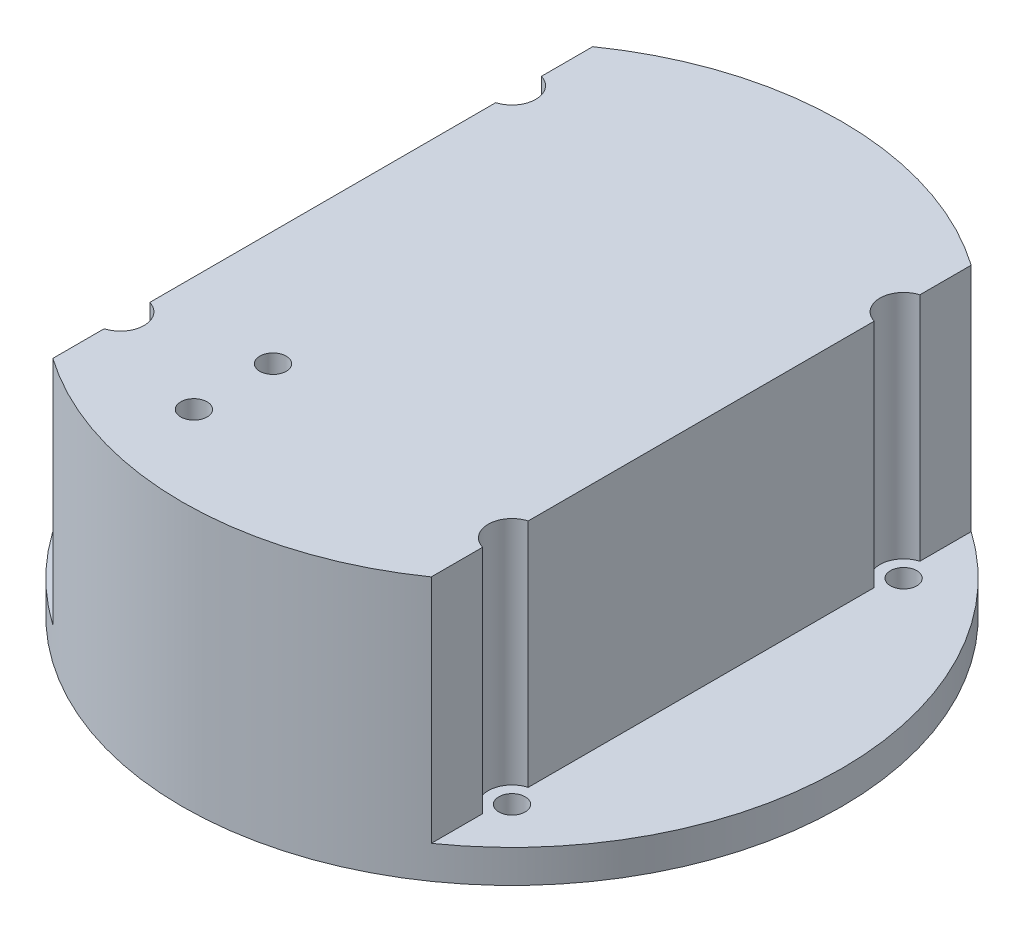
SolidWorks part; units mm, degrees
ref_plane "Ön Düzlem" through (0, 0, 0) normal (0, 0, 1) x (1, 0, 0)
ref_plane "Üst Düzlem" through (0, 0, 0) normal (0, 1, 0) x (1, 0, 0)
ref_plane "Sağ Düzlem" through (0, 0, 0) normal (1, 0, 0) x (0, 0, -1)
sketch "ara düzlem" plane through (0, 0, 0) normal (0, 1, 0) x (1, 0, 0)
  line L0 (-28.7, 40.9428) -> (-28.7, -40.9428)
  line L1 (0, 0) -> (0, 50) construction
  line L2 (28.7, 40.9428) -> (28.7, -40.9428)
  circle A0 centre (0, 0) radius 50
  point P5 (14.6186, 0)
  point P8 (-50, 0)
  point P11 (-28.7, 0)
  dimension "D1" = 100
  dimension "D2" = 21.3
extrude "base" add sketch "ara düzlem" along normal blind 5 contours L0 A0 | L2 A0 L0 | L2 A0 region at (0, 0, 0) region at (-37.3976, 0, 0) region at (37.3976, 0, 0)
extrude "Yükseklik-Ekstrüzyon2" add sketch "Çizim1<3>" along normal blind 40 contours L2 A0 L0 region at (0, 0, 0)
sketch "Çizim1<3>" plane through (0, 0, 0) normal (0, 1, 0) x (1, 0, 0) same geometry as "ara düzlem"
sketch "Çizim2" plane through (0, 40, 0) normal (0, 1, 0) x (1, 0, 0)
  line L0 (-11.3, -30.9428) -> (28.7, -30.9428) construction
  line L2 (28.7, 40.9428) -> (28.7, -40.9428) construction
  circle A0 centre (-11.3, -24.9428) radius 2
  circle A2 centre (-11.3, -36.9428) radius 2
  dimension "D1" = 4
  dimension "D2" = 6
  dimension "D3" = 40
  dimension "D4" = 10
extrude "banana slotları" cut sketch "Çizim2" against normal through all
sketch "Çizim3" plane through (0, 0, 0) normal (0, -1, 0) x (1, 0, 0)
  circle A0 centre (0, 0) radius 42 construction
  circle A1 centre (-29.6985, 29.6985) radius 2
  circle A5 centre (0, 0) radius 50 construction
  circle A6 centre (29.6985, 29.6985) radius 2
  circle A7 centre (29.6985, -29.6985) radius 2
  circle A8 centre (-29.6985, -29.6985) radius 2
  circle A9 centre (0, 0) radius 5.05
  point P16 (0, 0)
  dimension "D1" = 4
  dimension "D2" = 8
  dimension "D4" = 10.1
  dimension "D3" = 4
sketch "Çizim4" plane through (0, 5, 0) normal (0, 1, 0) x (1, 0, 0)
  point P0 (-28.7, 0)
extrude "Kes-Ekstrüzyon1" cut sketch "Çizim3" against normal blind 5
extrude "Kes-Ekstrüzyon2" cut sketch "Çizim3<2>" against normal through all contours A1 | A8 | A7 | A6 region at (-29.6985, 0, 29.6985) region at (29.6985, 0, 29.6985) region at (29.6985, 0, -29.6985) region at (-29.6985, 0, -29.6985)
sketch "Çizim3<2>" plane through (0, 0, 0) normal (0, -1, 0) x (1, 0, 0) same geometry as "Çizim3"
sketch "Çizim5" plane through (0, 5, 0) normal (0, 1, 0) x (1, 0, 0)
  circle A0 centre (29.6985, -29.6985) radius 3.6
  arc A1 (28.7, -31.4314) -> (28.7, -27.9656) centre (29.6985, -29.6985) ccw construction
  circle A2 centre (-29.6985, -29.6985) radius 3.6
  circle A3 centre (-29.6985, 29.6985) radius 3.6
  circle A4 centre (29.6985, 29.6985) radius 3.6
  point P5 (-29.6985, -29.6985)
  point P13 (0, 0)
  dimension "D1" = 7.2
  dimension "D2" = 4
extrude "Kes-Ekstrüzyon3" cut sketch "Çizim5" along normal through all
